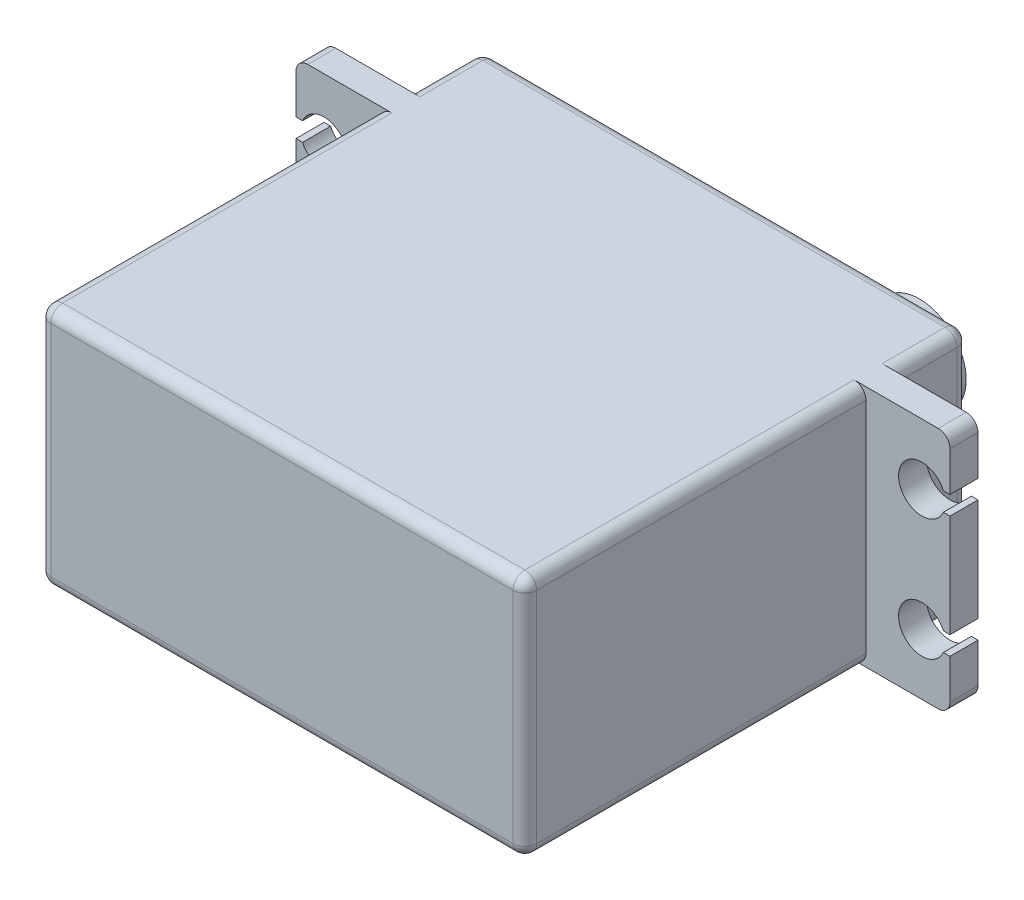
SolidWorks part; units mm, degrees
ref_plane "Front Plane" through (0, 0, 0) normal (0, 0, 1) x (1, 0, 0)
ref_plane "Top Plane" through (0, 0, 0) normal (0, 1, 0) x (1, 0, 0)
ref_plane "Right Plane" through (0, 0, 0) normal (1, 0, 0) x (0, 0, -1)
sketch "Sketch1" plane through (0, 0, 0) normal (0, 1, 0) x (1, 0, 0)
  line L0 (-41.275, 28.9719) -> (0, 28.9719) construction
  line L1 (0, 0) -> (-41.275, 0)
  line L2 (0, 0) -> (0, 28.9719)
  line L3 (0, 37.7031) -> (-41.275, 37.7031)
  line L4 (-41.275, 0) -> (-41.275, 28.9719)
  line L5 (-20.6375, 37.7031) -> (-20.6375, 0) construction
  line L6 (0, 28.9719) -> (7.1437, 28.9719)
  line L7 (-41.275, 31.3531) -> (-48.4187, 31.3531)
  line L8 (0, 31.3531) -> (0, 37.7031)
  line L9 (-41.275, 28.9719) -> (-48.4187, 28.9719)
  line L10 (-48.4187, 31.3531) -> (-48.4187, 28.9719)
  line L11 (7.1437, 31.3531) -> (7.1437, 28.9719)
  line L12 (0, 31.3531) -> (7.1437, 31.3531)
  line L13 (-41.275, 31.3531) -> (-41.275, 37.7031)
  dimension "D1" = 41.275
  dimension "D2" = 37.7031
  dimension "D3" = 28.9719
  dimension "D4" = 7.1437
  dimension "D5" = 2.3813
extrude "Boss-Extrude1" add sketch "Sketch1" along normal blind 20.6375
sketch "Sketch2" plane through (0, 0, -31.3531) normal (0, 0, -1) x (-1, 0, 0)
  line L0 (-7.1437, 10.3187) -> (48.4187, 10.3187) construction
  line L1 (-7.1437, 20.6375) -> (-7.1437, 0) construction
  line L2 (48.4187, 20.6375) -> (48.4187, 0) construction
  line L3 (0, 20.6375) -> (0, 0) construction
  line L4 (20.6375, 20.6375) -> (20.6375, 0) construction
  line L5 (0, 20.6375) -> (41.275, 20.6375) construction
  line L6 (0, 0) -> (41.275, 0) construction
  line L7 (-4.7625, 15.4781) -> (46.0375, 15.4781) construction
  line L8 (-7.1437, 16.2719) -> (-6.5812, 16.2719)
  line L9 (-7.1437, 14.6844) -> (-6.5812, 14.6844)
  line L10 (47.8562, 16.2719) -> (48.4187, 16.2719)
  line L11 (47.8562, 14.6844) -> (48.4187, 14.6844)
  line L12 (48.4187, 14.6844) -> (48.4187, 16.2719)
  line L13 (-7.1437, 14.6844) -> (-7.1437, 16.2719)
  line L14 (47.8562, 4.3656) -> (48.4187, 4.3656)
  line L15 (48.4187, 5.9531) -> (48.4187, 4.3656)
  line L16 (47.8562, 5.9531) -> (48.4187, 5.9531)
  line L17 (-7.1437, 5.9531) -> (-6.5812, 5.9531)
  line L18 (-7.1437, 5.9531) -> (-7.1437, 4.3656)
  line L19 (-7.1437, 4.3656) -> (-6.5812, 4.3656)
  arc A0 (-6.5812, 14.6844) -> (-6.5812, 16.2719) centre (-4.7625, 15.4781) ccw
  arc A1 (-6.5812, 5.9531) -> (-6.5812, 4.3656) centre (-4.7625, 5.1594) cw
  arc A2 (47.8562, 14.6844) -> (47.8562, 16.2719) centre (46.0375, 15.4781) cw
  arc A3 (47.8562, 5.9531) -> (47.8562, 4.3656) centre (46.0375, 5.1594) ccw
  dimension "D1" = 3.9688
  dimension "D2" = 5.1594
  dimension "D3" = 4.7625
  dimension "D4" = 0.7937
extrude "Cut-Extrude1" cut sketch "Sketch2" against normal through all
fillet "Fillet1" radius 1 4 edges at (-48.4187, 20.6375, -30.1625) (-48.4187, 0, -30.1625) (7.1437, 0, -30.1625) (7.1437, 20.6375, -30.1625)
fillet "Fillet2" radius 1 16 edges at (-20.6375, 0, -37.7031) (-20.6375, 20.6375, -37.7031) (-41.275, 10.3187, -37.7031) (0, 10.3187, -37.7031) (-41.275, 0, -34.5281) (-41.275, 20.6375, -34.5281) (0, 0, -34.5281) (0, 20.6375, -34.5281) (0, 0, -14.4859) (0, 20.6375, -14.4859) (0, 10.3187, 0) (-20.6375, 20.6375, 0) (-20.6375, 0, 0) (-41.275, 10.3187, 0) (-41.275, 20.6375, -14.4859) (-41.275, 0, -14.4859)
sketch "Sketch3" plane through (0, 0, -37.7031) normal (0, 0, -1) x (-1, 0, 0)
  line L0 (1, 10.3187) -> (40.275, 10.3187) construction
  line L1 (1, 19.6375) -> (1, 1) construction
  line L2 (40.275, 1) -> (40.275, 19.6375) construction
  circle A0 centre (10.525, 10.3187) radius 4.7625
  dimension "D1" = 9.525
  dimension "D2" = 9.525
extrude "Boss-Extrude2" add sketch "Sketch3" along normal blind 3.175
fillet "Fillet3" radius 1 1 edges at (-5.7625, 10.3187, -37.7031)
sketch "Sketch4" plane through (0, 0, -40.8781) normal (0, 0, -1) x (-1, 0, 0)
  circle A0 centre (10.525, 10.3187) radius 3.9688
  dimension "D1" = 7.9375
extrude "Boss-Extrude3" add sketch "Sketch4" along normal blind 3.175
